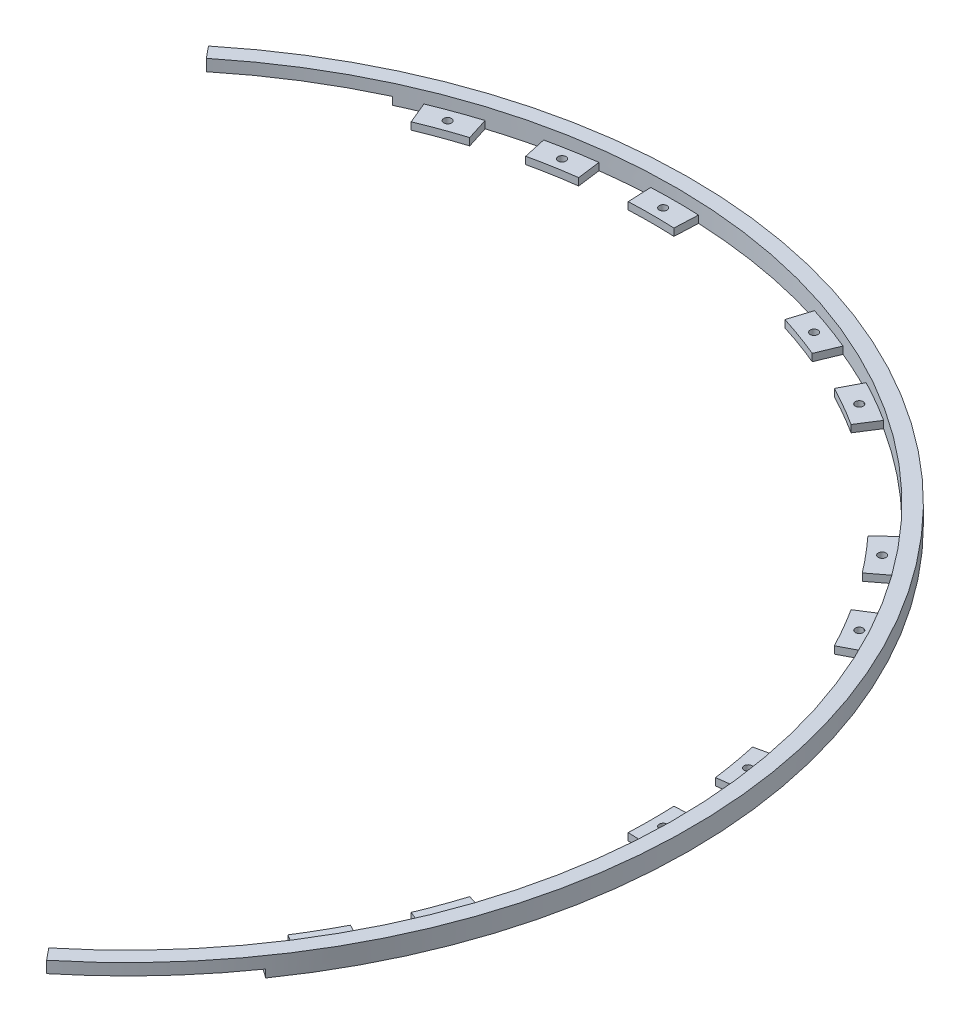
SolidWorks part; units mm, degrees
material "6061-T6 AL"
ref_plane "Front" through (0, 0, 0) normal (0, 0, 1) x (1, 0, 0)
ref_plane "Top" through (0, 0, 0) normal (0, 1, 0) x (1, 0, 0)
ref_plane "Right" through (0, 0, 0) normal (1, 0, 0) x (0, 0, -1)
other "Bounding Box"
ref_plane "Default Plane" through (-1310.244, 15.875, 1561.5197) normal (-0.0872, 0, -0.9962) x (-0.9962, 0, 0.0872)
ref_axis "Axis1" through (0, 57.3504, 0) along (0, -1, 0)
sketch "Sketch1" plane through (0, 0, 0) normal (0, 0, 1) x (1, 0, 0)
  line L1 (0, 0) -> (718.175, 0) construction
  line L2 (687.2625, 0) -> (687.2625, -9.525)
  line L3 (718.175, 0) -> (738.0625, 0) construction
  line L4 (718.175, 0) -> (718.175, 15.875)
  line L5 (718.175, 15.875) -> (738.0625, 15.875)
  line L6 (738.0625, 0) -> (738.0625, 15.875)
  line L11 (687.2625, -9.525) -> (738.0625, -9.525)
  line L12 (687.2625, 0) -> (718.175, 0)
  line L13 (738.0625, -9.525) -> (738.0625, 0)
  dimension "D1" = 718.175
  dimension "D2" = 15.875
  dimension "D3" = 687.2625
  dimension "D4" = 25.4
  dimension "D5" = 50.8
revolve "Revolve1" add sketch "Sketch1" angle 360 about axis through (0, 57.3504, 0) along (0, -1, 0)
sketch "Sketch6" plane through (0, 0, 0) normal (0, 1, 0) x (1, 0, 0)
  line L0 (0, 0) -> (702.5, 0) construction
  point P2 (702.5, 0)
  point P10 (702.5, 0)
  dimension "D1" = 702.5
hole_wizard "3/8 Clearance Hole1" positions "Sketch6" profile "Sketch7" hole size "3/8" standard "ANSI Inch" end condition through all
sketch "Sketch7" plane through (702.5, 0, 0) normal (1, 0, 0) x (0, 0, 1)
  line L0 (0, 0) -> (0, 9.525)
  line L1 (0, 9.525) -> (5.1587, 9.525)
  line L2 (5.1587, 9.525) -> (5.1587, 0)
  line L5 (5.1587, 0) -> (0, 0)
  line L11 (0, -6.35) -> (0, 107.95) construction
  dimension "Thru Hole Dia." = 10.3175
  dimension "Thru Hole Depth" = 9.525
sketch "Sketch16" plane through (0, 0, 0) normal (0, 1, 0) x (1, 0, 0)
  line L0 (712.0309, -93.7406) -> (681.3829, -89.7058)
  line L9 (717.4915, -31.3264) -> (686.6084, -29.978)
  line L10 (0, 0) -> (681.3829, -89.7058)
  line L11 (0, 0) -> (686.6084, -29.978)
  line L12 (0, 0) -> (625.9439, 0) construction
  circle A0 centre (0, 0) radius 718.175 construction
  arc A2 (717.4915, -31.3264) -> (712.0309, -93.7406) centre (0, 0) cw
  circle A4 centre (0, 0) radius 687.2625 construction
  dimension "D1" = 2.5
  dimension "D2" = 5
extrude "Cut-Extrude1" cut sketch "Sketch16" against normal through all
pattern_circular "CirPattern1" count 36 over 360 about axis through (0, 0, 0) along (0, 1, 0) of "3/8 Clearance Hole1", "Cut-Extrude1"
sketch "Sketch18" plane through (0, -9.525, 0) normal (0, -1, 0) x (1, 0, 0)
  line L1 (303.5139, 650.8876) -> (0, 0) construction
  line L2 (0, 0) -> (588.2945, 411.9283) construction
  arc A0 (303.5139, 650.8876) -> (588.2945, 411.9283) centre (0, 0) cw
  arc A1 (331.6163, 637.029) -> (274.8337, 663.5072) centre (0, 0) ccw construction
  arc A3 (605.7027, 385.8751) -> (569.7665, 437.1972) centre (0, 0) ccw construction
extrude "Cut-Extrude-Thin1" cut sketch "Sketch18" against normal blind 10.16 and the other way through all thin
pattern_circular "CirPattern3" count 2 over 360 about axis through (0, 0, 0) along (0, 1, 0) of "Cut-Extrude-Thin1"
sketch "Sketch41" plane through (0, -9.525, 0) normal (0, -1, 0) x (1, 0, 0)
  line L0 (693.7038, 185.8774) -> (663.8446, 177.8766)
  line L1 (715.4421, 62.5931) -> (684.6473, 59.8989)
  line L2 (701.1514, 155.4415) -> (670.9716, 148.7508) construction
  line L3 (693.7038, -185.8774) -> (663.8446, -177.8766)
  line L4 (650.8876, -303.5139) -> (622.8714, -290.4497)
  line L5 (507.8264, -507.8264) -> (485.968, -485.968)
  line L6 (411.9283, -588.2945) -> (394.1976, -562.9725)
  line L7 (185.8774, -693.7038) -> (177.8766, -663.8446)
  line L8 (62.5931, -715.4421) -> (59.8989, -684.6473)
  line L9 (-185.8774, -693.7038) -> (-177.8766, -663.8446) [skipped]
  line L10 (-303.5139, -650.8876) -> (-290.4497, -622.8714) [skipped]
  line L11 (-507.8264, -507.8264) -> (-485.968, -485.968) [skipped]
  line L12 (-588.2945, -411.9283) -> (-562.9725, -394.1976) [skipped]
  line L13 (-693.7038, -185.8774) -> (-663.8446, -177.8766)
  line L14 (-715.4421, -62.5931) -> (-684.6473, -59.8989)
  line L15 (-693.7038, 185.8774) -> (-663.8446, 177.8766)
  line L16 (-650.8876, 303.5139) -> (-622.8714, 290.4497)
  line L17 (-507.8264, 507.8264) -> (-485.968, 485.968)
  line L18 (-411.9283, 588.2945) -> (-394.1976, 562.9725)
  line L19 (-185.8774, 693.7038) -> (-177.8766, 663.8446)
  line L20 (-62.5931, 715.4421) -> (-59.8989, 684.6473)
  line L21 (0, 0) -> (684.6473, 59.8989) construction
  line L22 (0, 0) -> (622.8714, -290.4497) construction
  arc A0 (715.4421, 62.5931) -> (693.7038, 185.8774) centre (0, 0) ccw
  arc A1 (684.6473, 59.8989) -> (663.8446, 177.8766) centre (0, 0) ccw
  arc A2 (650.8876, -303.5139) -> (693.7038, -185.8774) centre (0, 0) ccw
  circle A3 centre (0, 0) radius 718.175 construction
  arc A4 (622.8714, -290.4497) -> (663.8446, -177.8766) centre (0, 0) ccw
  arc A5 (411.9283, -588.2945) -> (507.8264, -507.8264) centre (0, 0) ccw
  arc A6 (394.1976, -562.9725) -> (485.968, -485.968) centre (0, 0) ccw
  arc A7 (62.5931, -715.4421) -> (185.8774, -693.7038) centre (0, 0) ccw
  arc A8 (59.8989, -684.6473) -> (177.8766, -663.8446) centre (0, 0) ccw
  arc A9 (-303.5139, -650.8876) -> (-185.8774, -693.7038) centre (0, 0) ccw [skipped]
  arc A10 (-290.4497, -622.8714) -> (-177.8766, -663.8446) centre (0, 0) ccw [skipped]
  arc A11 (-588.2945, -411.9283) -> (-507.8264, -507.8264) centre (0, 0) ccw [skipped]
  arc A12 (-562.9725, -394.1976) -> (-485.968, -485.968) centre (0, 0) ccw [skipped]
  arc A13 (-715.4421, -62.5931) -> (-693.7038, -185.8774) centre (0, 0) ccw
  arc A14 (-684.6473, -59.8989) -> (-663.8446, -177.8766) centre (0, 0) ccw
  arc A15 (-650.8876, 303.5139) -> (-693.7038, 185.8774) centre (0, 0) ccw
  arc A16 (-622.8714, 290.4497) -> (-663.8446, 177.8766) centre (0, 0) ccw
  arc A17 (-411.9283, 588.2945) -> (-507.8264, 507.8264) centre (0, 0) ccw
  arc A18 (-394.1976, 562.9725) -> (-485.968, 485.968) centre (0, 0) ccw
  arc A19 (-62.5931, 715.4421) -> (-185.8774, 693.7038) centre (0, 0) ccw
  arc A20 (-59.8989, 684.6473) -> (-177.8766, 663.8446) centre (0, 0) ccw
  dimension "D1" = 10
  dimension "D2" = 2.5
  dimension "D3" = 30
extrude "Cut-Extrude3" cut sketch "Sketch41" against normal through all
ref_plane "Plane1" through (0, 0.635, 0) normal (0, -1, 0) x (-1, 0, 0)
sketch "Sketch42" plane through (0, 15.875, 0) normal (0, 1, 0) x (1, 0, 0)
  line L0 (466.0988, -572.2658) -> (-466.0988, 572.2658)
  circle A0 centre (0, 0) radius 738.0625 construction
  arc A1 (-466.0988, 572.2658) -> (466.0988, -572.2658) centre (0, 0) cw
  point P7 (0, 0)
  circle M1 centre (0, 0) radius 718.175
  circle M2 centre (0, 0) radius 738.0625
extrude "Cut-Extrude4" cut sketch "Sketch42" against normal through all contours L0 M1 | L0 M2 M1
